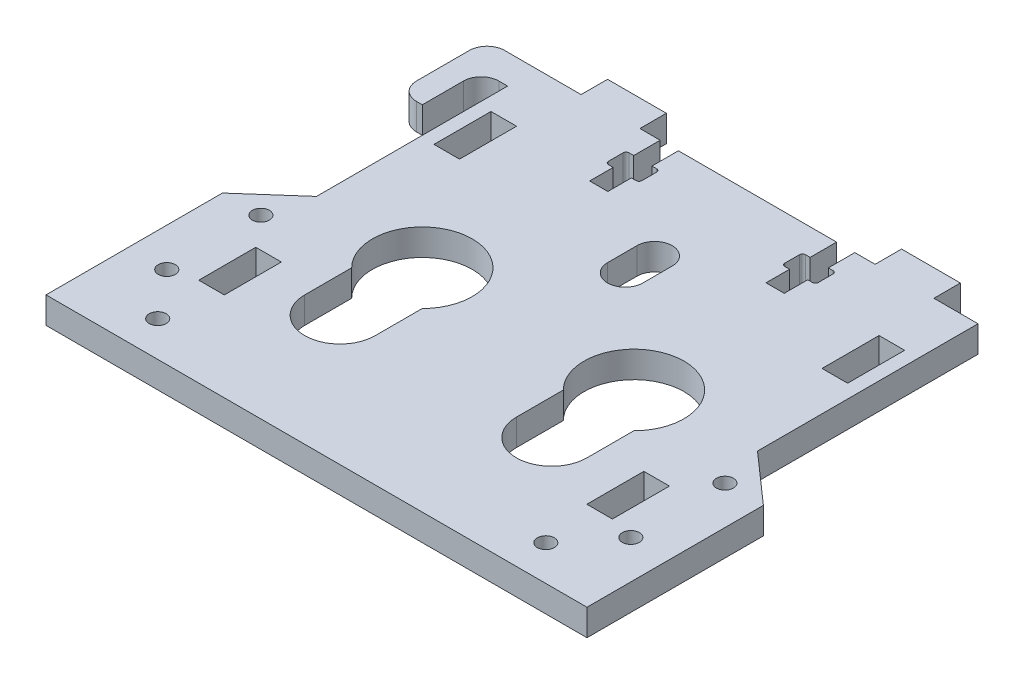
SolidWorks part; units mm, degrees
ref_plane "Front Plane" through (0, 0, 0) normal (0, 0, 1) x (1, 0, 0)
ref_plane "Top Plane" through (0, 0, 0) normal (0, 1, 0) x (1, 0, 0)
ref_plane "Right Plane" through (0, 0, 0) normal (1, 0, 0) x (0, 0, -1)
sketch "Sketch1" plane through (0, 0, 0) normal (0, 1, 0) x (1, 0, 0)
  line L1 (-37.5, 37.5) -> (37.5, 37.5)
  line L2 (-37.5, 37.5) -> (-37.5, -37.5)
  line L3 (-37.5, -37.5) -> (37.5, -37.5)
  line L4 (37.5, 37.5) -> (37.5, -37.5)
  line L5 (-37.5, 37.5) -> (37.5, -37.5) construction
  line L6 (-37.5, -37.5) -> (37.5, 37.5) construction
  point P0 (0, 0)
  dimension "D1" = 75
  dimension "D2" = 75
extrude "MainShape" add sketch "Sketch1" along normal blind 4.5
sketch "Sketch2" plane through (0, 4.5, 0) normal (0, 1, 0) x (1, 0, 0)
  line L0 (0, -37.5) -> (0, 37.5) construction
  line L1 (-37.5, -37.5) -> (37.5, -37.5) construction
  line L2 (37.5, 37.5) -> (-37.5, 37.5) construction
  line L4 (-5, 42) -> (5, 42)
  line L5 (-5, 42) -> (-5, 33)
  line L6 (-5, 33) -> (5, 33)
  line L7 (5, 42) -> (5, 33)
  line L8 (-5, 42) -> (5, 33) construction
  line L9 (-5, 33) -> (5, 42) construction
  dimension "D1" = 10
  dimension "D2" = 4.5
extrude "Tab1" [suppressed] add sketch "Sketch2" against normal through all
sketch "Sketch4" [suppressed] plane through (0, 4.5, 0) normal (0, 1, 0) x (1, 0, 0)
  line L0 (0, 42) -> (0, -37.5) construction
  line L1 (5, 42) -> (-5, 42) construction
  line L2 (-47.5, -37.5) -> (47.5, -37.5) construction
  line L3 (-40, 37.5) -> (-40, 27) construction
  line L4 (-5, 37.5) -> (-47.5, 37.5) construction
  line L5 (-38.25, 27) -> (-41.75, 27) construction
  line L6 (-41.75, 27) -> (-41.75, 37.5) construction
  line L7 (-38.25, 27) -> (-41.75, 27)
  line L8 (-41.75, 27) -> (-41.75, 29.5)
  line L9 (-41.75, 29.5) -> (-42.75, 29.5)
  line L10 (-43, 29.75) -> (-43, 33.45)
  line L11 (-42.75, 33.7) -> (-41.75, 33.7)
  line L12 (-41.75, 33.7) -> (-41.75, 37.5)
  line L13 (-41.75, 37.5) -> (-38.25, 37.5)
  line L14 (-38.25, 27) -> (-38.25, 37.5) construction
  line L15 (-38.25, 33.7) -> (-38.25, 37.5)
  line L16 (-37.25, 33.7) -> (-38.25, 33.7)
  line L17 (-37, 29.75) -> (-37, 33.45)
  line L18 (-38.25, 29.5) -> (-37.25, 29.5)
  line L19 (-38.25, 27) -> (-38.25, 29.5)
  line L20 (38.25, 27) -> (38.25, 37.5) construction
  line L21 (41.75, 27) -> (41.75, 37.5) construction
  line L22 (38.25, 27) -> (41.75, 27) construction
  line L23 (40, 37.5) -> (40, 27) construction
  line L24 (38.25, 27) -> (38.25, 29.5)
  line L25 (38.25, 29.5) -> (37.25, 29.5)
  line L26 (37, 29.75) -> (37, 33.45)
  line L27 (37.25, 33.7) -> (38.25, 33.7)
  line L28 (38.25, 33.7) -> (38.25, 37.5)
  line L29 (41.75, 37.5) -> (38.25, 37.5)
  line L30 (41.75, 33.7) -> (41.75, 37.5)
  line L31 (42.75, 33.7) -> (41.75, 33.7)
  line L32 (43, 29.75) -> (43, 33.45)
  line L33 (41.75, 29.5) -> (42.75, 29.5)
  line L34 (41.75, 27) -> (41.75, 29.5)
  line L35 (38.25, 27) -> (41.75, 27)
  arc A0 (-42.75, 29.5) -> (-43, 29.75) centre (-42.75, 29.75) cw
  arc A1 (-37, 29.75) -> (-37.25, 29.5) centre (-37.25, 29.75) cw
  arc A2 (-37.25, 33.7) -> (-37, 33.45) centre (-37.25, 33.45) cw
  arc A3 (-43, 33.45) -> (-42.75, 33.7) centre (-42.75, 33.45) cw
  arc A4 (43, 33.45) -> (42.75, 33.7) centre (42.75, 33.45) ccw
  arc A5 (37.25, 33.7) -> (37, 33.45) centre (37.25, 33.45) ccw
  arc A6 (37, 29.75) -> (37.25, 29.5) centre (37.25, 29.75) ccw
  arc A7 (42.75, 29.5) -> (43, 29.75) centre (42.75, 29.75) ccw
  point P24 (-43, 29.5)
  point P27 (-37, 29.5)
  point P30 (-37, 33.7)
  point P33 (-43, 33.7)
  point P56 (43, 33.7)
  point P57 (37, 33.7)
  point P58 (37, 29.5)
  point P59 (43, 29.5)
  dimension "D7" = 0.5
  dimension "D1" = 11
  dimension "D2" = 1.55
  dimension "D3" = 3.5
  dimension "D4" = 2.85
  dimension "D5" = 8
  dimension "D6" = 40
extrude "Cut-Extrude2" [suppressed] cut sketch "Sketch4" against normal through all
sketch "Sketch5" plane through (0, 4.5, 0) normal (0, 1, 0) x (1, 0, 0)
  line L0 (0, -37.5) -> (0, 37.5) construction
  line L1 (-37.5, -37.5) -> (37.5, -37.5) construction
  line L3 (33, 37.5) -> (33, -37.5) construction
  line L4 (37.5, 37.5) -> (-37.5, 37.5) construction
  line L5 (-33, 37.5) -> (-33, -37.5) construction
  line L6 (30.825, 27.35) -> (35.175, 27.35)
  line L7 (30.825, 27.35) -> (30.825, 17.65)
  line L8 (30.825, 17.65) -> (35.175, 17.65)
  line L9 (35.175, 27.35) -> (35.175, 17.65)
  line L10 (30.825, 27.35) -> (35.175, 17.65) construction
  line L11 (30.825, 17.65) -> (35.175, 27.35) construction
  line L12 (-30.825, 17.65) -> (-35.175, 27.35) construction
  line L13 (-30.825, 27.35) -> (-35.175, 17.65) construction
  line L14 (-35.175, 27.35) -> (-35.175, 17.65)
  line L15 (-30.825, 17.65) -> (-35.175, 17.65)
  line L16 (-30.825, 27.35) -> (-30.825, 17.65)
  line L17 (-30.825, 27.35) -> (-35.175, 27.35)
  line L18 (-37.5, 2.5) -> (37.5, 2.5) construction
  line L19 (-37.5, 37.5) -> (-37.5, -37.5) construction
  line L20 (37.5, -37.5) -> (37.5, 37.5) construction
  line L21 (-30.825, -22.35) -> (-35.175, -12.65) construction
  line L22 (-30.825, -12.65) -> (-35.175, -22.35) construction
  line L23 (30.825, -12.65) -> (35.175, -22.35) construction
  line L24 (30.825, -22.35) -> (35.175, -12.65) construction
  line L25 (-30.825, -22.35) -> (-35.175, -22.35)
  line L26 (-30.825, -22.35) -> (-30.825, -12.65)
  line L27 (-30.825, -12.65) -> (-35.175, -12.65)
  line L28 (-35.175, -22.35) -> (-35.175, -12.65)
  line L29 (35.175, -22.35) -> (35.175, -12.65)
  line L30 (30.825, -12.65) -> (35.175, -12.65)
  line L31 (30.825, -22.35) -> (30.825, -12.65)
  line L32 (30.825, -22.35) -> (35.175, -22.35)
  line L33 (-30.825, 27.35) -> (-35.175, 17.65) construction
  line L34 (-37.5, 37.5) -> (37.5, 37.5) construction
  line L35 (37.5, 37.5) -> (-37.5, 37.5) construction
  point P10 (33, 22.5)
  point P21 (-33, 22.5)
  point P36 (-33, -17.5)
  point P37 (33, -17.5)
  dimension "D1" = 33
  dimension "D2" = 9.7
  dimension "D3" = 4.35
  dimension "D4" = 15
  dimension "D5" = 40
extrude "Cut-Extrude3" cut sketch "Sketch5" against normal through all
sketch "Sketch6" plane through (0, 4.5, 0) normal (0, 1, 0) x (1, 0, 0)
  line L0 (-18, -37.5) -> (-18, 28) construction
  line L1 (-24, -15.5) -> (-24, -7.5208)
  line L3 (-37.5, -15.5) -> (37.5, -15.5) construction
  line L4 (-37.5, 37.5) -> (-37.5, -37.5) construction
  line L5 (37.5, -37.5) -> (37.5, 37.5) construction
  line L6 (37.5, 37.5) -> (-37.5, 37.5) construction
  line L7 (-37.5, -37.5) -> (37.5, -37.5) construction
  line L8 (-12, -15.5) -> (-12, -7.5208)
  line L9 (-37.5, 37.5) -> (37.5, 37.5) construction
  arc A0 (-24, -15.5) -> (-12, -15.5) centre (-18, -15.5) ccw
  arc A2 (-12, -7.5208) -> (-24, -7.5208) centre (-18, -1.5) ccw
  dimension "D1" = 12
  dimension "D6" = 8.5
  dimension "D2" = 53
  dimension "D3" = 0
  dimension "D5" = 0
  dimension "D7" = 14
  dimension "D4" = 18
extrude "Cut-Extrude4" cut sketch "Sketch6" against normal through all
sketch "Sketch13" plane through (0, 4.5, 0) normal (0, 1, 0) x (1, 0, 0)
  line L0 (-37.5, 0) -> (-46, -7.5)
  line L1 (-37.5, 37.5) -> (-37.5, -37.5) construction
  line L2 (-46, -7.5) -> (-46, -37.5)
  line L3 (-46, -37.5) -> (-37.5, -37.5)
  line L4 (-37.5, -37.5) -> (-37.5, 0)
  line L5 (0, 37.5) -> (0, -37.5) construction
  line L6 (37.5, 37.5) -> (-37.5, 37.5) construction
  line L7 (-37.5, -37.5) -> (37.5, -37.5) construction
  line L8 (37.5, -37.5) -> (37.5, 0)
  line L9 (46, -37.5) -> (37.5, -37.5)
  line L10 (46, -7.5) -> (46, -37.5)
  line L11 (37.5, 0) -> (46, -7.5)
  line L12 (-37.5, -37.5) -> (-37.5, 0)
  line M23 (37.5, -37.5) -> (37.5, 37.5)
  line M25 (-37.5, 37.5) -> (-37.5, -37.5)
  dimension "D1" = 46
  dimension "D2" = 30
extrude "Boss-Extrude2" add sketch "Sketch13" against normal through all contours L2 L3 L0 M25 | L11 L9 L10 M23 region at (-41.5926, 4.5, 20.5556) region at (41.5926, 4.5, 20.5556)
sketch "Sketch8" plane through (0, 4.5, 0) normal (0, 1, 0) x (1, 0, 0)
  line L0 (-18, -9.5) -> (-18, -21.5) construction
  line L1 (-18, -15.5) -> (-39.46, -15.5) construction
  line L2 (-39.46, -23.5) -> (-39.46, -7.5) construction
  line L3 (-18, -21.5) -> (-18, -9.5) construction
  circle A0 centre (-39.46, -7.5) radius 1.45
  circle A1 centre (-18, -15.5) radius 6 construction
  circle A2 centre (-39.46, -23.5) radius 1.45
  dimension "D3" = 2.9
  dimension "D1" = 0
  dimension "D2" = 8
  dimension "D4" = 21.46
extrude "Cut-Extrude6" cut sketch "Sketch8" against normal through all
mirror "Mirror1" about plane through (0, 0, 0) normal (1, 0, 0) of "Cut-Extrude6", "Cut-Extrude4"
sketch "Sketch11" plane through (0, 4.5, 0) normal (0, 1, 0) x (1, 0, 0)
  line L0 (0, 37.5) -> (0, -37.5) construction
  line L1 (37.5, 37.5) -> (-37.5, 37.5) construction
  line L2 (-46, -37.5) -> (46, -37.5) construction
  line L3 (-25, 42) -> (-25, 37.5) construction
  line L4 (-30, 37.5) -> (-20, 37.5)
  line L5 (-30, 37.5) -> (-30, 42)
  line L6 (-30, 42) -> (-20, 42)
  line L7 (-20, 37.5) -> (-20, 42)
  line L8 (25, 42) -> (25, 37.5) construction
  line L9 (20, 37.5) -> (20, 42)
  line L10 (30, 42) -> (20, 42)
  line L11 (30, 37.5) -> (30, 42)
  line L12 (30, 37.5) -> (20, 37.5)
  dimension "D1" = 10
  dimension "D2" = 4.5
  dimension "D3" = 25
extrude "RearTabs" add sketch "Sketch11" against normal through all
sketch "Sketch12" plane through (0, 4.5, 0) normal (0, 1, 0) x (1, 0, 0)
  line L0 (-15, 0) -> (-15, 37.5) construction
  line L1 (20, 37.5) -> (-20, 37.5) construction
  line L2 (-13.45, 37.5) -> (-16.55, 37.5)
  line L3 (-16.55, 37.5) -> (-16.55, 33)
  line L4 (-16.55, 33) -> (-17.35, 33)
  line L5 (-17.85, 32.5) -> (-17.85, 30)
  line L6 (-17.35, 29.5) -> (-16.55, 29.5)
  line L7 (-16.55, 29.5) -> (-16.55, 25.5)
  line L8 (-16.55, 25.5) -> (-13.45, 25.5)
  line L9 (-13.45, 29.5) -> (-13.45, 25.5)
  line L10 (-12.65, 29.5) -> (-13.45, 29.5)
  line L11 (-12.15, 32.5) -> (-12.15, 30)
  line L12 (-13.45, 33) -> (-12.65, 33)
  line L13 (-13.45, 37.5) -> (-13.45, 33)
  line L14 (0, 37.5) -> (0, 23.4067) construction
  line L15 (13.45, 37.5) -> (13.45, 33)
  line L16 (13.45, 33) -> (12.65, 33)
  line L17 (12.15, 32.5) -> (12.15, 30)
  line L18 (12.65, 29.5) -> (13.45, 29.5)
  line L19 (13.45, 29.5) -> (13.45, 25.5)
  line L20 (16.55, 25.5) -> (13.45, 25.5)
  line L21 (16.55, 29.5) -> (16.55, 25.5)
  line L22 (17.35, 29.5) -> (16.55, 29.5)
  line L23 (17.85, 32.5) -> (17.85, 30)
  line L24 (16.55, 33) -> (17.35, 33)
  line L25 (16.55, 37.5) -> (16.55, 33)
  line L26 (13.45, 37.5) -> (16.55, 37.5)
  arc A0 (-17.85, 30) -> (-17.35, 29.5) centre (-17.35, 30) ccw
  arc A1 (-17.35, 33) -> (-17.85, 32.5) centre (-17.35, 32.5) ccw
  arc A2 (-12.65, 33) -> (-12.15, 32.5) centre (-12.65, 32.5) cw
  arc A3 (-12.15, 30) -> (-12.65, 29.5) centre (-12.65, 30) cw
  arc A4 (12.15, 30) -> (12.65, 29.5) centre (12.65, 30) ccw
  arc A5 (12.65, 33) -> (12.15, 32.5) centre (12.65, 32.5) ccw
  arc A6 (17.35, 33) -> (17.85, 32.5) centre (17.35, 32.5) cw
  arc A7 (17.85, 30) -> (17.35, 29.5) centre (17.35, 30) cw
  point P14 (-17.85, 29.5)
  point P17 (-17.85, 33)
  point P25 (-15, 25.5)
  point P28 (-12.15, 33)
  point P29 (-12.15, 29.5)
  point P53 (12.15, 29.5)
  point P54 (12.15, 33)
  point P55 (15, 25.5)
  point P56 (17.85, 33)
  point P57 (17.85, 29.5)
  dimension "D5" = 8
  dimension "D1" = 12
  dimension "D6" = 0.5
  dimension "D2" = 3.5
  dimension "D3" = 2.85
  dimension "D4" = 1.55
  dimension "D7" = 15
extrude "FrontScrewSlot" cut sketch "Sketch12" against normal through all
sketch "Sketch14" plane through (0, 4.5, 0) normal (0, 1, 0) x (1, 0, 0)
  line L0 (-33, 27.35) -> (-33, -37.5) construction
  line L1 (-30.825, 27.35) -> (-35.175, 27.35) construction
  line L2 (-46, -37.5) -> (46, -37.5) construction
  line L3 (-30, 37.5) -> (-37.5, 37.5) construction
  line L4 (0, 0) -> (0, -37.5) construction
  line L5 (33, 27.35) -> (33, -37.5) construction
  line L6 (-33, 27.35) -> (-33, -37.5) construction
  circle A0 centre (-33, -31.5) radius 1.45
  circle A1 centre (33, -31.5) radius 1.45
  dimension "D2" = 2.9
  dimension "D1" = 69
extrude "BraceScrews" cut sketch "Sketch14" against normal through all
sketch "Sketch15" plane through (0, 4.5, 0) normal (0, 1, 0) x (1, 0, 0)
  line L0 (0, -37.5) -> (0, 27.5) construction
  line L1 (-46, -37.5) -> (46, -37.5) construction
  line L3 (16, 27.5) -> (-16, 27.5) construction
  line L4 (-16.55, 37.5) -> (-20, 37.5) construction
  line L5 (-18.175, 32.35) -> (-13.825, 32.35)
  line L6 (-18.175, 32.35) -> (-18.175, 22.65)
  line L7 (-18.175, 22.65) -> (-13.825, 22.65)
  line L8 (-13.825, 32.35) -> (-13.825, 22.65)
  line L9 (-18.175, 32.35) -> (-13.825, 22.65) construction
  line L10 (-18.175, 22.65) -> (-13.825, 32.35) construction
  line L11 (18.175, 22.65) -> (13.825, 32.35) construction
  line L12 (18.175, 32.35) -> (13.825, 22.65) construction
  line L13 (13.825, 32.35) -> (13.825, 22.65)
  line L14 (18.175, 22.65) -> (13.825, 22.65)
  line L15 (18.175, 32.35) -> (18.175, 22.65)
  line L16 (18.175, 32.35) -> (13.825, 32.35)
  point P19 (0, 27.5)
  dimension "D1" = 16
  dimension "D2" = 4.35
  dimension "D3" = 9.7
  dimension "D4" = 10
extrude "FanTabs" [suppressed] cut sketch "Sketch15" against normal through all
sketch "Sketch16" plane through (0, 4.5, 0) normal (0, 1, 0) x (1, 0, 0)
  line L0 (0, 0) -> (0, 37.5) construction
  line L2 (0, 20) -> (0, 15) construction
  line L3 (3, 20) -> (3, 15)
  line L4 (-3, 20) -> (-3, 15)
  line L5 (13.45, 37.5) -> (-13.45, 37.5) construction
  arc A0 (3, 20) -> (-3, 20) centre (0, 20) ccw
  arc A1 (-3, 15) -> (3, 15) centre (0, 15) ccw
  point P7 (0, 17.5)
  dimension "D1" = 3
  dimension "D2" = 20
  dimension "D3" = 5
extrude "WiringSlot" cut sketch "Sketch16" against normal through all
sketch "Sketch17" [suppressed] plane through (0, 4.5, 0) normal (0, 1, 0) x (1, 0, 0)
  line L0 (-37.5, 14.5) -> (-37.5, 10.5) construction
  line L3 (-37.5, 37.5) -> (-37.5, 0) construction
  line L4 (-36, 14.5) -> (-36, 10.5)
  line L5 (-39, 14.5) -> (-39, 10.5)
  line L6 (-37.5, 14.5) -> (-37.5, 10.5) construction
  line L7 (-34, 14.5) -> (-34, 10.5)
  line L8 (-41, 14.5) -> (-41, 10.5)
  line L9 (-41, 12.5) -> (-37.5, 12.5) construction
  line L10 (0, 0) -> (0, -12.1805) construction
  arc A0 (-36, 14.5) -> (-39, 14.5) centre (-37.5, 14.5) ccw
  arc A1 (-39, 10.5) -> (-36, 10.5) centre (-37.5, 10.5) ccw
  arc A2 (-34, 14.5) -> (-41, 14.5) centre (-37.5, 14.5) ccw
  arc A3 (-41, 10.5) -> (-34, 10.5) centre (-37.5, 10.5) ccw
  point P4 (-37.5, 12.5)
  point P10 (-37.5, 12.5)
  dimension "D4" = 4
  dimension "D5" = 25
  dimension "D1" = 0
  dimension "D2" = 2
  dimension "D3" = 1.5
extrude "Boss-Extrude3" [suppressed] add sketch "Sketch17" against normal through all
mirror "Mirror2" [suppressed] about plane through (0, 0, 0) normal (1, 0, 0)
sketch "Sketch18" [suppressed] plane through (0, 4.5, 0) normal (0, 1, 0) x (1, 0, 0)
  line L0 (0, -37.5) -> (0, 47.6111) construction
  line L1 (-45, -37.5) -> (45, -37.5) construction
  line L2 (-12, 2) -> (-12, -19.46) construction
  line L3 (-4, -19.46) -> (-20, -19.46) construction
  circle A0 centre (-12, 2) radius 5
  circle A1 centre (-20, -19.46) radius 1.45
  circle A2 centre (-4, -19.46) radius 1.45
  dimension "D2" = 8
  dimension "D4" = 21.46
  dimension "D1" = 2.9
  dimension "D3" = 10
  dimension "D5" = 12
  dimension "D6" = 2
extrude "Cut-Extrude7" [suppressed] cut sketch "Sketch18" against normal through all
mirror "Mirror3" [suppressed] about plane through (0, 0, 0) normal (1, 0, 0)
sketch "Sketch19" [suppressed] plane through (0, 4.5, 0) normal (0, 1, 0) x (1, 0, 0)
  line L0 (-17, 2) -> (-7, 2) construction
  line L1 (-12, 2) -> (-4, 2) construction
  line L2 (-12, 4) -> (-4, 4)
  line L3 (-12, 0) -> (-4, 0)
  line L4 (-12, 7) -> (-12, -3) construction
  line L5 (0, 0) -> (0, 6.8806) construction
  line L6 (12, 7) -> (12, -3) construction
  line L7 (17, 2) -> (7, 2) construction
  line L8 (12, 2) -> (4, 2) construction
  line L9 (12, 4) -> (4, 4)
  line L10 (12, 0) -> (4, 0)
  circle A0 centre (-12, 2) radius 5 construction
  arc A1 (-12, 4) -> (-12, 0) centre (-12, 2) ccw
  arc A2 (-4, 0) -> (-4, 4) centre (-4, 2) ccw
  arc A3 (12, 4) -> (12, 0) centre (12, 2) cw
  arc A4 (4, 0) -> (4, 4) centre (4, 2) cw
  point P6 (-8, 2)
  point P23 (8, 2)
  dimension "D1" = 2
  dimension "D2" = 8
extrude "Cut-Extrude8" [suppressed] cut sketch "Sketch19" against normal through all
sketch "Sketch20" plane through (0, 4.5, 0) normal (0, 1, 0) x (1, 0, 0)
  line L0 (0, 0) -> (0, -37.5) construction
  line L1 (-46, -37.5) -> (46, -37.5) construction
  line L2 (-26.9758, -32.9017) -> (-26.9758, -26.6196)
  line L3 (-26.9758, -26.6196) -> (-6.5592, -26.6196)
  line L4 (-6.5592, -26.6196) -> (-6.5592, 9.4097)
  line L5 (-6.5592, 9.4097) -> (6.5592, 9.4097)
  line L6 (-26.9758, -32.9017) -> (26.9758, -32.9017)
  line L7 (6.5592, -26.6196) -> (6.5592, 9.4097)
  line L8 (26.9758, -26.6196) -> (6.5592, -26.6196)
  line L9 (26.9758, -32.9017) -> (26.9758, -26.6196)
  point P12 (0, -32.9017)
  point P13 (0, 9.4097)
extrude "Cut-Extrude9" [suppressed] cut sketch "Sketch20" against normal through all
sketch "Sketch21" plane through (0, 4.5, 0) normal (0, 1, 0) x (1, 0, 0)
  line L0 (-46, -37.5) -> (-46, 37.5) construction
  line L1 (-37, 37.5) -> (-43, 37.5)
  line L4 (-46, 34.5) -> (-46, 25.5)
  line L5 (-43, 22.5) -> (-42, 22.5)
  line L6 (-42, 22.5) -> (-42, 29.5)
  line L7 (-39, 32.5) -> (-37, 32.5)
  line L9 (-37, 32.5) -> (-37, 37.5)
  line L10 (-30, 37.5) -> (-37.5, 37.5) construction
  line L11 (-37.5, 37.5) -> (-37.5, 0) construction
  arc A0 (-42, 29.5) -> (-39, 32.5) centre (-39, 29.5) cw
  arc A1 (-46, 25.5) -> (-43, 22.5) centre (-43, 25.5) ccw
  arc A2 (-43, 37.5) -> (-46, 34.5) centre (-43, 34.5) ccw
  point P19 (-46, 22.5)
  point P24 (-42, 37.5)
  dimension "D1" = 3
  dimension "D4" = 3
  dimension "D2" = 15
  dimension "D3" = 5
  dimension "D5" = 4
  dimension "D6" = 0.5
  dimension "D7" = 0
extrude "Boss-Extrude4" add sketch "Sketch21" against normal through all
sketch "Sketch22" plane through (0, 4.5, 0) normal (0, 1, 0) x (1, 0, 0)
  line L0 (-46, -7.5) -> (-46, 13.5)
  line L1 (-43, 16.5) -> (-42, 16.5)
  line L2 (-42, 16.5) -> (-42, -3.9706)
  line L3 (-37.5, 0) -> (-46, -7.5) construction
  line L4 (-42, -3.9706) -> (-46, -7.5)
  line L5 (-46, 16.5) -> (-46, 28.3122) construction
  line L6 (-46, 34.5) -> (-46, 25.5) construction
  line L7 (-42, 22.6875) -> (-42, 12.0504) construction
  line L8 (-42, 22.5) -> (-42, 29.5) construction
  arc A0 (-46, 13.5) -> (-43, 16.5) centre (-43, 13.5) cw
  dimension "D2" = 3
  dimension "D1" = 6
extrude "Boss-Extrude5" [suppressed] add sketch "Sketch22" against normal through all
mirror "Mirror6" [suppressed] about plane through (0, 0, 0) normal (1, 0, 0)
equation "\"X-ROD-SPACING\"=45"
equation "\"Y-ROD-SPACING\"=75"
equation "\"Z-ROD-SPACING\"=17.5"
equation "\"Y-BED-OFFSET\"=2"
equation "\"Y-BED-ROD-INSET\"=3.5"
equation "\"Y-BED-SCREW-SPACING\"=209"
equation "\"Y-BED-SCREW-CUTOUT-SLOT-HEIGHT\"=2.5"
equation "\"T-SLOT-NUT-FILLET-RADIUS\"=0.5"
equation "\"T-SLOT-SCREW-SHAFT-RADIUS\"=1.55"
equation "\"T-SLOT-SCREW-SHAFT-CUTOUT-LENGTH\"=11"
equation "\"T-SLOT-NUT-DEPTH\"=3.5"
equation "\"T-SLOT-NUT-WIDTH\"=2.85"
equation "\"T-SLOT-NUT-END-DISTANCE\"=8"
equation "\"ACRYLIC-THICKNESS\"=10"
equation "\"ACRYLIC-THICKNESS2\"=4.5"
equation "\"ACRYLIC-TAB-CUTOUT-SIZE\"=\"ACRYLIC-THICKNESS\"+\"ACRYLIC-TAB-TOLERANCE\"*2"
equation "\"ACRYLIC-TAB-WIDTH\"=\"ACRYLIC-THICKNESS\""
equation "\"ACRYLIC-M3-HOLE\"=2.9"
equation "\"SMOOTHROD-CAP-SCREW-DISTANCE\"=20"
equation "\"FRAME-WIDTH-INNER\"=370"
equation "\"NEMA17-HOLE-SPACING\"=31"
equation "\"NEMA17-CENTRAL-CUTOUT\"=22.5"
equation "\"Z-BRACKET-REACH\"=57"
equation "\"Z-ROD-INSET\"=13.5"
equation "\"TOP-BRACKET-SPACING\"=40"
equation "\"SMOOTHROD-X-LENGTH\"=350"
equation "\"SMOOTHROD-Y-LENGTH\"=350"
equation "\"SMOOTHROD-Z-LENGTH\"=350"
equation "\"SMOOTHROD-TIGHTENING-HEADROOM\"=.25"
equation "\"LEADSCREW-Z-LENGTH\"=300"
equation "\"SCREW-LENGTH-FRAME\"=\"ACRYLIC-THICKNESS\" + 10"
equation "\"SCREW-LENGTH-MOTOR\"=\"ACRYLIC-THICKNESS\" + 5"
equation "\"SCREW-LENGTH-EXTRUDER\"=28"
equation "\"SCREW-HEAD-RADIUS\"=6"
equation "\"PRINTED-X-SMOOTHROD-DIAMETER\"=8.8"
equation "\"PRINTED-X-SMOOTHROD-CUTOUT\"=10"
equation "\"PRINTED-X-BASE-HEIGHT\"=10"
equation "\"PRINTED-LM8UU-CUTOUT-SIZE\"=15.5"
equation "\"PRINTED-LM8UU-CUTOUT-LENGTH\"=24.5"
equation "\"PRINTED-X-IDLER-HEIGHT\"=16"
equation "\"PSU-MOUNTING-WIDTH\"=95"
equation "\"PSU-MOUNTING-HEIGHT\"=177"
equation "\"Y-BELT-TO-ROD-DISTANCE\"=20"
equation "\"SPOOL-HOLDER-ROD-SPACING\"=150"
equation "\"ACRYLIC-X-CARRIAGE-WIDTH\"=55"
equation "\"ACRYLIC-X-CARRIAGE-HEIGHT\"=75"
equation "\"ACRYLIC-X-CARRIAGE-SCREW-SPACING-X\"=15"
equation "\"ACRYLIC-X-CARRIAGE-SCREW-SPACING-Y\"=33"
equation "\"ACRYLIC-X-CARRIAGE-CENTER-TAB-SPACING\"=14"
equation "\"D1@MainShape\" = \"ACRYLIC-THICKNESS2\""
equation "\"D1@Sketch2\"=\"ACRYLIC-TAB-WIDTH\""
equation "\"D2@Sketch2\"=\"ACRYLIC-THICKNESS2\""
equation "\"D1@Sketch4\"=\"T-SLOT-SCREW-SHAFT-CUTOUT-LENGTH\""
equation "\"D2@Sketch4\"=\"T-SLOT-SCREW-SHAFT-RADIUS\""
equation "\"D3@Sketch4\"=\"T-SLOT-NUT-DEPTH\""
equation "\"D4@Sketch4\"=\"T-SLOT-NUT-WIDTH\""
equation "\"D5@Sketch4\"=\"T-SLOT-NUT-END-DISTANCE\""
equation "\"D7@Sketch4\"=\"T-SLOT-NUT-FILLET-RADIUS\""
equation "\"ACRYLIC-X-CARRIAGE-EXTRUDER-SHELF-DEPTH\"=\"ACRYLIC-X-CARRIAGE-EXTRUDER-OFFSET\" + 28"
equation "\"ACRYLIC-X-CARRIAGE-LM8UU-CUTOUT-WIDTH\"=24.25"
equation "\"ACRYLIC-X-CARRIAGE-EXTRUDER-BRACE-SPACING\"=23"
equation "\"ACRYLIC-X-CARRIAGE-EXTRUDER-BRACE-TAB-OFFSET\"=20"
equation "\"ACRYLIC-X-CARRIAGE-EXTRUDER-BRACE-HEIGHT\"=35"
equation "\"ACRYLIC-X-CARRIAGE-EXTRUDER-BRACE-SCREW-SPACING\"=22"
equation "\"D2@Sketch5\"=\"ACRYLIC-THICKNESS2-TAB-CUTOUT-HEIGHT\""
equation "\"D3@Sketch5\"=\"ACRYLIC-THICKNESS2-TAB-CUTOUT-WIDTH\""
equation "\"D3@Sketch8\"=\"ACRYLIC-M3-HOLE\""
equation "\"ACRYLIC-X-CARRIAGE-EXTRUDER-ANGLE\"=90"
equation "\"ACRYLIC-X-CARRIAGE-EXTRUDER-OFFSET\"=26"
equation "\"ACRYLIC-TAB-TOLERANCE\"=-.05"
equation "\"ACRYLIC-X-CARRIAGE-DUAL-WIDTH-MULTIPLIER\"=1.65"
equation "\"ACRYLIC-X-CARRIAGE-DUAL-HOTEND-SPACING\"=42"
equation "\"ACRYLIC-X-CARRIAGE-DUAL-WIDTH\"=75"
equation "\"ACRYLIC-X-CARRIAGE-DUAL-HOTEND-SEPARATION\"=36"
equation "\"ACRYLIC-X-CARRIAGE-DUAL-MOUNT-PLATE-DEPTH\"=75"
equation "\"ACRYLIC-X-CARRIAGE-DUAL-MOUNT-BRACE-WIDTH\"=33"
equation "\"D1@Sketch5\"=\"ACRYLIC-X-CARRIAGE-DUAL-MOUNT-BRACE-WIDTH\""
equation "\"ACRYLIC-X-CARRIAGE-DUAL-MOUNT-SCREW-WIDTH\"=40"
equation "\"D6@Sketch4\"=\"ACRYLIC-X-CARRIAGE-DUAL-MOUNT-SCREW-WIDTH\""
equation "\"D1@Sketch1\"=\"ACRYLIC-X-CARRIAGE-DUAL-WIDTH\""
equation "\"D2@Sketch1\"=\"ACRYLIC-X-CARRIAGE-DUAL-MOUNT-PLATE-DEPTH\""
equation "\"D4@Sketch6\"=\"ACRYLIC-X-CARRIAGE-DUAL-HOTEND-SEPARATION\"/2"
equation "\"D1@Sketch11\"=\"ACRYLIC-TAB-WIDTH\""
equation "\"D2@Sketch11\"=\"ACRYLIC-THICKNESS2\""
equation "\"D1@Sketch12\"=\"T-SLOT-SCREW-SHAFT-CUTOUT-LENGTH\"+1"
equation "\"D2@Sketch12\"=\"T-SLOT-NUT-DEPTH\""
equation "\"D3@Sketch12\"=\"T-SLOT-NUT-WIDTH\""
equation "\"D4@Sketch12\"=\"T-SLOT-SCREW-SHAFT-RADIUS\""
equation "\"D5@Sketch12\"=\"T-SLOT-NUT-END-DISTANCE\""
equation "\"D6@Sketch12\"=\"T-SLOT-NUT-FILLET-RADIUS\""
equation "\"D2@Sketch14\"=\"ACRYLIC-M3-HOLE\""
equation "\"D2@Sketch15\"=\"ACRYLIC-THICKNESS2-TAB-CUTOUT-WIDTH\""
equation "\"D3@Sketch15\"=\"ACRYLIC-THICKNESS2-TAB-CUTOUT-HEIGHT\""
equation "\"KERF\"=0.075"
equation "\"PRINTED-M3-HOLE\"=3.5"
equation "\"PRINTED-M3-NUT-AF\"=6.25"
equation "\"ACRYLIC-X-CARRIAGE-LM8UU-CUTOUT-HEIGHT\"=11.0"
equation "\"ACRYLIC-X-CARRIAGE-DUAL-FAN-OFFSET\"=52"
equation "\"ACRYLIC-X-CARRIAGE-DUAL-FAN-HEIGHT\"=20"
equation "\"BLOWER-FAN-WIDTH\"=15"
equation "\"ACRYLIC-THICKNESS-TAB-CUTOUT-WIDTH\"=\"ACRYLIC-THICKNESS\"-\"KERF\"*2"
equation "\"ACRYLIC-THICKNESS-TAB-CUTOUT-HEIGHT\"=\"ACRYLIC-TAB-WIDTH\"-\"KERF\"*4"
equation "\"ACRYLIC-THICKNESS2-TAB-CUTOUT-WIDTH\"=\"ACRYLIC-THICKNESS2\"-\"KERF\"*2"
equation "\"ACRYLIC-THICKNESS2-TAB-CUTOUT-HEIGHT\"=\"ACRYLIC-TAB-WIDTH\"-\"KERF\"*4"
equation "\"D1@Sketch18\"=\"ACRYLIC-M3-HOLE\""
equation "\"D7@Sketch12\"=\"ACRYLIC-X-CARRIAGE-SCREW-SPACING-X\""
